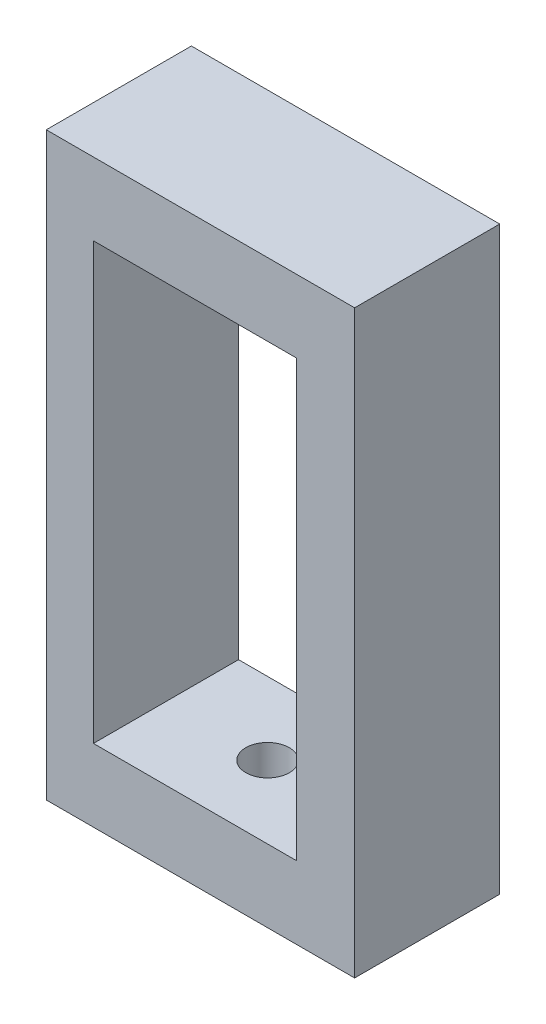
SolidWorks part; units mm, degrees
material "Brass"
ref_plane "Front Plane" through (0, 0, 0) normal (0, 0, 1) x (1, 0, 0)
ref_plane "Top Plane" through (0, 0, 0) normal (0, 1, 0) x (1, 0, 0)
ref_plane "Right Plane" through (0, 0, 0) normal (1, 0, 0) x (0, 0, -1)
sketch "Sketch1" plane through (0, 0, 0) normal (0, 0, 1) x (1, 0, 0)
  line L0 (0.75, 0) -> (22, 0)
  line L1 (22, 0) -> (22, 40)
  line L2 (22, 40) -> (0.75, 40)
  line L3 (0.75, 40) -> (0.75, 0)
  line L4 (4, 5) -> (18, 5)
  line L5 (18, 5) -> (18, 35)
  line L6 (18, 35) -> (4, 35)
  line L7 (4, 35) -> (4, 5)
  dimension "D1" = 21.25
  dimension "D2" = 40
  dimension "D3" = 0.75
  dimension "D4" = 14
  dimension "D5" = 30
  dimension "D6" = 4
  dimension "D7" = 5
extrude "Boss-Extrude1" add sketch "Sketch1" along normal blind 10
sketch "Sketch2" plane through (0, 0, 0) normal (0, 1, 0) x (1, 0, 0)
  circle A0 centre (11, -5) radius 1.5
  dimension "D3" = 3
  dimension "D1" = 11
  dimension "D2" = 5
extrude "Cut-Extrude1" cut sketch "Sketch2" against normal mid plane 30
